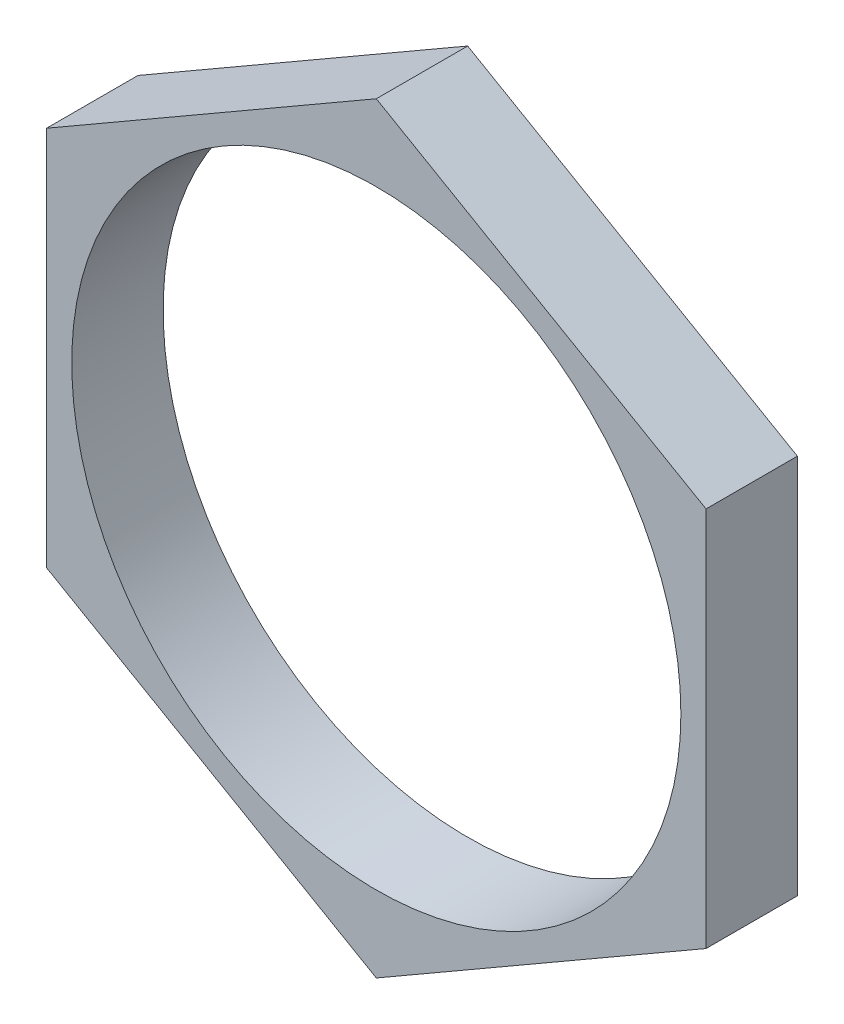
SolidWorks part; units mm, degrees
ref_plane "Front Plane" through (0, 0, 0) normal (0, 0, 1) x (1, 0, 0)
ref_plane "Top Plane" through (0, 0, 0) normal (0, 1, 0) x (1, 0, 0)
ref_plane "Right Plane" through (0, 0, 0) normal (1, 0, 0) x (0, 0, -1)
sketch "Sketch1" plane through (0, 0, 0) normal (0, 0, 1) x (1, 0, 0)
  line L0 (0, 0) -> (0, 12.5) construction
  line L1 (10.8253, -6.25) -> (10.8253, 6.25)
  line L2 (10.8253, 6.25) -> (0, 12.5)
  line L3 (0, 12.5) -> (-10.8253, 6.25)
  line L4 (-10.8253, 6.25) -> (-10.8253, -6.25)
  line L5 (-10.8253, -6.25) -> (0, -12.5)
  line L6 (0, -12.5) -> (10.8253, -6.25)
  circle A0 centre (0, 0) radius 10.8253 construction
  circle A1 centre (0, 0) radius 10
  dimension "D2" = 20
  dimension "D1" = 25
extrude "Boss-Extrude1" add sketch "Sketch1" along normal blind 3
